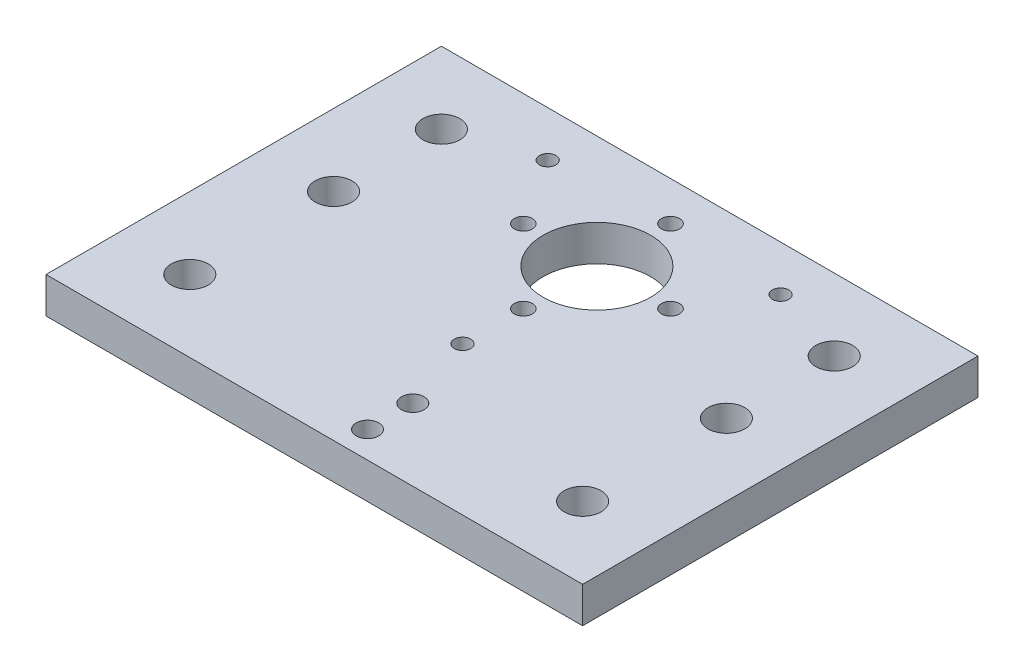
SolidWorks part; units mm, degrees
ref_plane "Front Plane" through (0, 0, 0) normal (0, 0, 1) x (1, 0, 0)
ref_plane "Top Plane" through (0, 0, 0) normal (0, 1, 0) x (1, 0, 0)
ref_plane "Right Plane" through (0, 0, 0) normal (1, 0, 0) x (0, 0, -1)
sketch "Sketch1" plane through (0, 0, 0) normal (0, 1, 0) x (1, 0, 0)
  line L0 (-34.7, 3.175) -> (34.7, 3.175) construction
  line L1 (-47.4, 34.925) -> (47.4, 34.925)
  line L2 (-47.4, 34.925) -> (-47.4, -34.925)
  line L3 (-47.4, -34.925) -> (47.4, -34.925)
  line L4 (47.4, 34.925) -> (47.4, -34.925)
  line L5 (-47.4, 34.925) -> (47.4, -34.925) construction
  line L6 (-47.4, -34.925) -> (47.4, 34.925) construction
  line L7 (22, -34.925) -> (47.4, -34.925) construction
  line L8 (4.7, -30.225) -> (4.7, -22.225) construction
  line L9 (-34.7, -22.225) -> (34.7, -22.225) construction
  line L10 (-34.7, -22.225) -> (-34.7, 22.225) construction
  line L11 (-34.7, 22.225) -> (34.7, 22.225) construction
  line L12 (34.7, -22.225) -> (34.7, 22.225) construction
  line L13 (-34.7, -22.225) -> (34.7, 22.225) construction
  line L14 (-34.7, 22.225) -> (34.7, -22.225) construction
  line L15 (0, 0) -> (0, 15) construction
  line L16 (4.7, -30.225) -> (18.2, -30.225) construction
  line L17 (22, -34.925) -> (22, -9.525) construction
  line L18 (22, -9.525) -> (47.4, -9.525) construction
  line L19 (47.4, -34.925) -> (47.4, -9.525) construction
  line L20 (22, -34.925) -> (47.4, -9.525) construction
  line L21 (22, -9.525) -> (47.4, -34.925) construction
  line L22 (0, 15) -> (0, -8.75) construction
  line L23 (0, 15) -> (20.5681, 26.875) construction
  line L24 (0, 15) -> (-20.5681, 26.875) construction
  circle A18 centre (-34.7, 22.225) radius 3.2576
  circle A19 centre (34.7, 22.225) radius 3.2576
  circle A20 centre (34.7, -22.225) radius 3.2576
  circle A21 centre (-34.7, -22.225) radius 3.2576
  circle A22 centre (4.7, -30.225) radius 2
  circle A23 centre (4.7, -22.225) radius 2
  circle A24 centre (0, 15) radius 9.5
  circle A25 centre (0, 15) radius 23.75 construction
  circle A30 centre (-34.7, 3.175) radius 3.2576
  circle A31 centre (34.7, 3.175) radius 3.2576
  circle A32 centre (0, -8.75) radius 1.45
  circle A33 centre (-20.5681, 26.875) radius 1.45
  circle A34 centre (20.5681, 26.875) radius 1.45
  point P50 (0, -8.75)
  point P51 (-20.8848, 26.3087)
  dimension "D2" = 30
  dimension "D4" = 19
  dimension "D7" = 47.5
  dimension "D10" = 120
  dimension "D13" = 12.7
  dimension "D15" = 6.5151
  dimension "D16" = 8
  dimension "D17" = 4
  dimension "D9" = 120
  dimension "D5" = 15
  dimension "D12" = 2.9
  dimension "D6" = 94.8
  dimension "D8" = 69.85
  dimension "D11" = 25.4
  dimension "D14" = 12.7
  dimension "D3" = 13.5
extrude "Boss-Extrude1" add sketch "Sketch1" along normal blind 6.35
hole_wizard "CSK for M3 Flat Head Machine Screw1" positions "Sketch7" profile "Sketch8" countersink size "M3" standard "ANSI Metric" end condition through all
sketch "Sketch7" plane through (0, 0, 0) normal (0, -1, 0) x (-1, 0, 0)
  point P0 (-13, 15)
  point P3 (0, 2)
  point P6 (13, 15)
  point P9 (0, 28)
sketch "Sketch8" plane through (13, 0, -15) normal (1, 0, 0) x (0, 0, -1)
  line L0 (0, 0) -> (0, 6.35)
  line L1 (0, 6.35) -> (1.6, 6.35)
  line L2 (1.6, 6.35) -> (1.6, 1.55)
  line L3 (1.6, 1.55) -> (3.15, 0)
  line L5 (3.15, 0) -> (0, 0)
  line L6 (-1.6, 1.55) -> (-3.15, 0) construction
  line L11 (0, -6.35) -> (0, 107.95) construction
  dimension "Thru Hole Dia." = 3.2
  dimension "Thru Hole Depth" = 6.35
  dimension "Near C'Sink Dia." = 6.3
  dimension "Near C'Sink Angle" = 90
equation "\"testbed_height\" = 91.50mm"
equation "\"plate_thickness\" = 6mm"
equation "\"main_body_splay_length\" = 48.5mm"
equation "\"splay_shaft_length_no_wires\" = 10mm"
equation "\"splay_shaft_length_wires\" = 6.5mm"
equation "\"timing_pulley_offset\" = 0mm"
equation "\"effective_motor_length\" = \"timing_pulley_offset\" + \"splay_shaft_length_no_wires\" + \"main_body_splay_length\""
equation "\"80_20_side\" = 25.4mm"
equation "\"80_20_length\" = 152.4mm"
equation "\"80_20_optic_mount_length\" = \"80_20_length\" - 25.4mm"
equation "\"optic_board_hole_size\" = 6.35mm"
equation "\"total_mounting_length\" = \"testbed_height\" - \"effective_motor_length\" - \"80_20_side\""
equation "\"mounting_vertical_portion_height\" = \"total_mounting_length\" - 2 * \"plate_thickness\""
equation "\"face_mount_width\" = 15.25mm"
equation "\"center_dist_to_face_mount_vertical_screws\" = 5mm"
equation "\"D1@Boss-Extrude1\"=0.25in"
